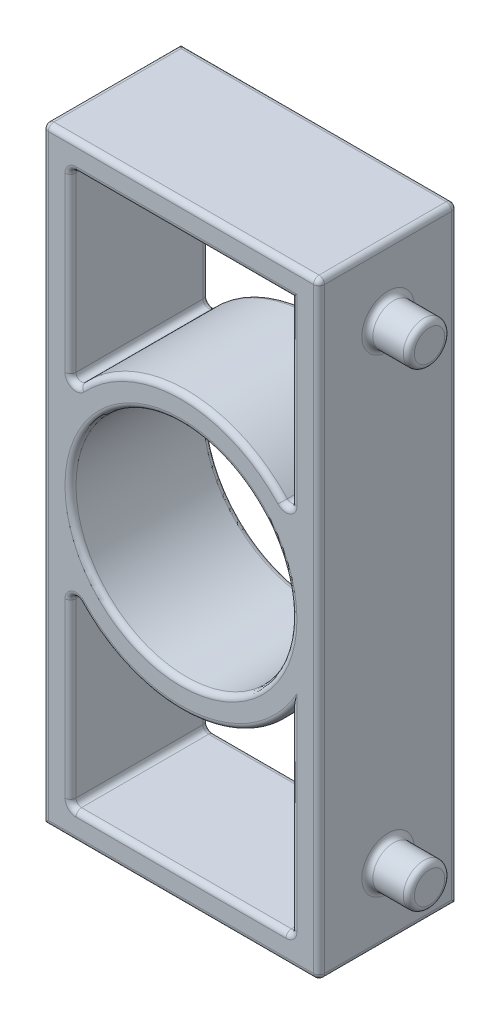
SolidWorks part; units mm, degrees
ref_plane "Front Plane" through (0, 0, 0) normal (0, 0, 1) x (1, 0, 0)
ref_plane "Top Plane" through (0, 0, 0) normal (0, 1, 0) x (1, 0, 0)
ref_plane "Right Plane" through (0, 0, 0) normal (1, 0, 0) x (0, 0, -1)
sketch "Sketch1" plane through (0, 0, 0) normal (1, 0, 0) x (0, 0, -1)
  line L1 (25, -110) -> (-25, -110)
  line L2 (25, -110) -> (25, 110)
  line L3 (25, 110) -> (-25, 110)
  line L4 (-25, -110) -> (-25, 110)
  line L5 (25, -110) -> (-25, 110) construction
  line L6 (25, 110) -> (-25, -110) construction
  point P0 (0, 0)
  dimension "D1" = 50
  dimension "D2" = 220
extrude "Boss-Extrude1" add sketch "Sketch1" along normal mid plane 100
sketch "Sketch2" plane through (50, 0, 0) normal (1, 0, 0) x (0, 0, -1)
  line L0 (0, 85) -> (0, -85) construction
  line L1 (0, 0) -> (50000, 0) construction
  circle A0 centre (0, 85) radius 7.5
  circle A1 centre (0, -85) radius 7.5
  point P7 (0, 0)
  dimension "D2" = 15
  dimension "D1" = 170
extrude "Boss-Extrude2" add sketch "Sketch2" along normal blind 15
mirror "Mirror1" about plane through (0, 0, 0) normal (1, 0, 0) of "Boss-Extrude2"
sketch "Sketch3" plane through (0, 0, -25) normal (0, 0, -1) x (-1, 0, 0)
  circle A0 centre (0, 0) radius 40
  point P3 (0, 0)
  dimension "D1" = 80
extrude "Cut-Extrude1" cut sketch "Sketch3" against normal through all
sketch "Sketch4" plane through (0, 0, -25) normal (0, 0, -1) x (-1, 0, 0)
  line L4 (-40, -30) -> (-40, -100)
  line L5 (40, 30) -> (40, 100)
  line L8 (40, -100) -> (40, 100)
  line L9 (40, 100) -> (-40, 100)
  line L10 (-40, 100) -> (-40, -100)
  line L11 (-40, -100) -> (40, -100)
  line L12 (40, -100) -> (40, -30)
  line L13 (40, 100) -> (-40, 100)
  line L14 (-40, 100) -> (-40, 30)
  line L15 (-40, -100) -> (40, -100)
  arc A1 (40, 30) -> (-40, 30) centre (0, 0) ccw
  circle A2 centre (0, 0) radius 50
  arc A3 (-40, -30) -> (40, -30) centre (0, 0) ccw
  dimension "D1" = 10
  dimension "D2" = 10
extrude "Cut-Extrude2" cut sketch "Sketch4" against normal through all
fillet "Fillet1" radius 2 41 edges at (40, -65, -25) (0, -50, -25) (40, 65, -25) (0, 100, -25) (0, -100, -25) (-40, -65, -25) (0, -50, 25) (40, -65, 25) (0, -100, 25) (-40, -65, 25) (40, -100, 0) (-40, -100, 0) (-40, -30, 0) (0, 50, -25) (-40, 65, -25) (0, 50, 25) (-40, 65, 25) (0, 100, 25) (40, 65, 25) (-40, 30, 0) (-40, 100, 0) (40, 30, 0) (-40, 0, -25) (-40, 0, 25) (-50, -85, -7.5) (-65, -85, -7.5) (-50, 85, -7.5) (-65, 85, -7.5) (50, -85, -7.5) (65, -85, -7.5) (50, 85, -7.5) (65, 85, -7.5) (-50, 0, 25) (-50, 110, 0) (50, 0, 25) (50, -110, 0) (50, 0, -25) (50, 110, 0) (0, 110, 25) (0, 110, -25) (0, -110, 25)
